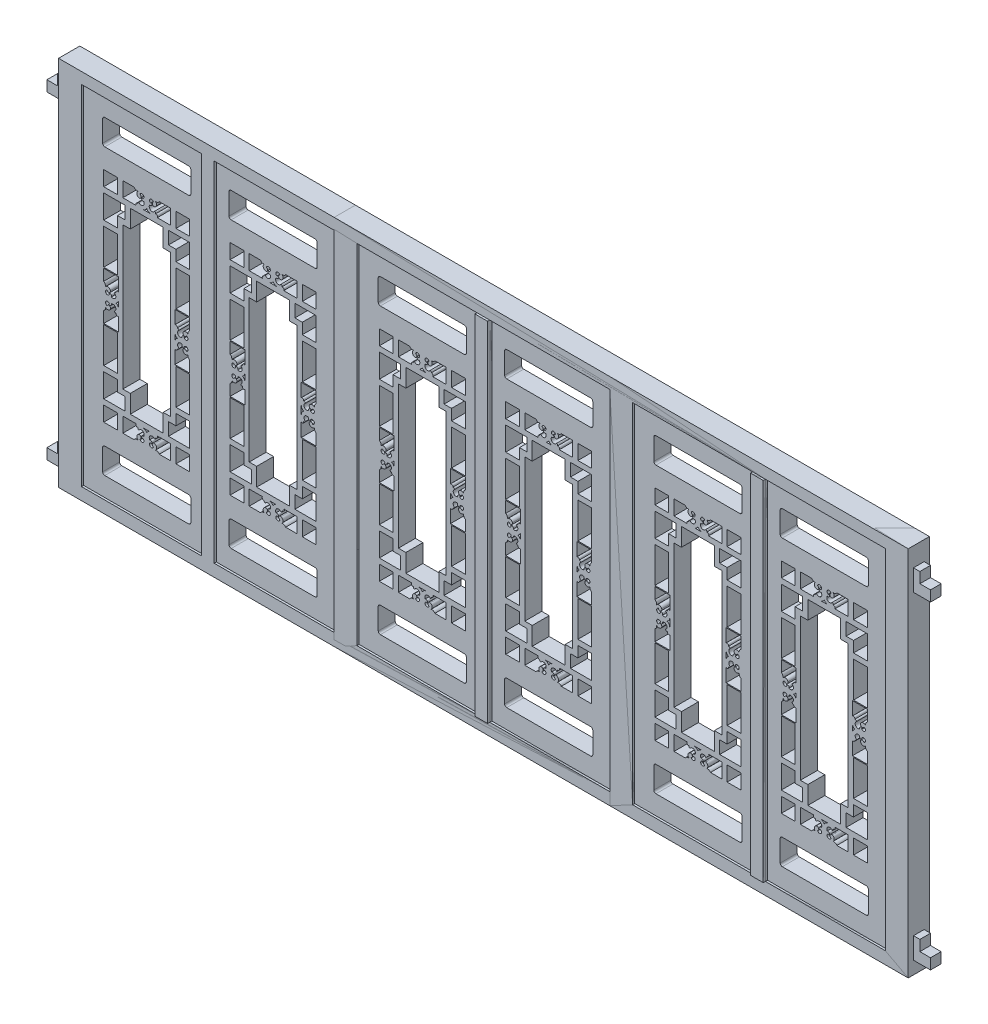
SolidWorks part; units mm, degrees
material "松木"
ref_plane "前视基准面" through (0, 0, 0) normal (0, 0, 1) x (1, 0, 0)
ref_plane "上视基准面" through (0, 0, 0) normal (0, 1, 0) x (1, 0, 0)
ref_plane "右视基准面" through (0, 0, 0) normal (1, 0, 0) x (0, 0, -1)
sketch "Sketch1" plane through (0, 0, 0) normal (0, 0, 1) x (1, 0, 0)
  line L0 (0, 0) -> (0, 1640)
  line L1 (0, 1640) -> (595, 1640)
  line L2 (595, 1640) -> (595, 0)
  line L3 (595, 0) -> (0, 0)
  dimension "D1" = 1640
  dimension "D2" = 595
extrude "Boss-Extrude1" add sketch "Sketch1" along normal blind 180
sketch "Sketch2" plane through (0, 0, 0) normal (0, 0, -1) x (-1, 0, 0)
  line L0 (-525, 1570) -> (-525, 70)
  line L1 (-525, 70) -> (-70, 70)
  line L2 (-70, 70) -> (-70, 1570)
  line L3 (-70, 1570) -> (-525, 1570)
  line L4 (-595, 0) -> (-595, 1640) construction
  line L5 (-595, 1640) -> (0, 1640) construction
  line L6 (-70, 1410) -> (-525, 1410)
  line L7 (-525, 230) -> (-70, 230)
  line L8 (-70, 1360) -> (-525, 1360)
  line L9 (-70, 280) -> (-525, 280)
  line L10 (-500, 1335) -> (-500, 305)
  line L11 (-500, 305) -> (-95, 305)
  line L12 (-95, 305) -> (-95, 1335)
  line L13 (-95, 1335) -> (-500, 1335)
  line L14 (-95, 1265) -> (-500, 1265)
  line L15 (-95, 1240) -> (-500, 1240)
  line L16 (-95, 375) -> (-500, 375)
  line L17 (-95, 400) -> (-500, 400)
  line L18 (-160, 1335) -> (-160, 1265)
  line L19 (-435, 1335) -> (-435, 1265)
  line L20 (-410, 1335) -> (-410, 1265)
  line L21 (-185, 1335) -> (-185, 1265)
  line L22 (-435, 375) -> (-435, 305)
  line L23 (-410, 375) -> (-410, 305)
  line L24 (-160, 375) -> (-160, 305)
  line L25 (-185, 375) -> (-185, 305)
  line L26 (-195, 400) -> (-195, 460)
  line L27 (-195, 460) -> (-160, 460)
  line L28 (-160, 460) -> (-160, 1180)
  line L29 (-160, 1180) -> (-195, 1180)
  line L30 (-195, 1180) -> (-195, 1240)
  line L31 (-400, 1240) -> (-400, 1180)
  line L32 (-400, 1180) -> (-435, 1180)
  line L33 (-435, 1180) -> (-435, 460)
  line L34 (-435, 460) -> (-400, 460)
  line L35 (-400, 460) -> (-400, 400)
  line L36 (-220, 1240) -> (-220, 1155)
  line L37 (-220, 1155) -> (-185, 1155)
  line L38 (-185, 1155) -> (-185, 485)
  line L39 (-185, 485) -> (-220, 485)
  line L40 (-220, 485) -> (-220, 400)
  line L41 (-375, 1240) -> (-375, 1155)
  line L42 (-375, 1155) -> (-410, 1155)
  line L43 (-410, 1155) -> (-410, 485)
  line L44 (-410, 485) -> (-375, 485)
  line L45 (-375, 485) -> (-375, 400)
  line L46 (-435, 1129) -> (-500, 1129)
  line L47 (-435, 1104) -> (-500, 1104)
  line L48 (-160, 1129) -> (-95, 1129)
  line L49 (-160, 1104) -> (-95, 1104)
  line L50 (-435, 511) -> (-500, 511)
  line L51 (-435, 536) -> (-500, 536)
  line L52 (-160, 511) -> (-95, 511)
  line L53 (-160, 536) -> (-95, 536)
  line L54 (-435, 937) -> (-500, 937)
  line L55 (-435, 919.4131) -> (-500, 919.4131)
  line L56 (-435, 703) -> (-500, 703)
  line L57 (-435, 728) -> (-500, 728)
  line L58 (-160, 919.4131) -> (-95, 919.4131)
  line L59 (-160, 937) -> (-95, 937)
  line L60 (-160, 703) -> (-95, 703)
  line L61 (-160, 728) -> (-95, 728)
  line L62 (-495, 210) -> (-100, 210)
  line L63 (-90, 200) -> (-90, 100)
  line L64 (-100, 90) -> (-495, 90)
  line L65 (-505, 100) -> (-505, 200)
  line L67 (-495, 1550) -> (-100, 1550)
  line L68 (-505, 1540) -> (-505, 1440)
  line L69 (-495, 1430) -> (-100, 1430)
  line L70 (-90, 1540) -> (-90, 1440)
  arc A0 (-495, 210) -> (-505, 200) centre (-495, 200) ccw
  arc A1 (-90, 200) -> (-100, 210) centre (-100, 200) ccw
  arc A2 (-505, 100) -> (-495, 90) centre (-495, 100) ccw
  arc A3 (-100, 90) -> (-90, 100) centre (-100, 100) ccw
  arc A4 (-495, 1550) -> (-505, 1540) centre (-495, 1540) ccw
  arc A5 (-90, 1540) -> (-100, 1550) centre (-100, 1540) ccw
  arc A6 (-505, 1440) -> (-495, 1430) centre (-495, 1440) ccw
  arc A7 (-100, 1430) -> (-90, 1440) centre (-100, 1440) ccw
  point P62 (-177.5, 1180)
  point P63 (-220, 442.5)
  point P64 (-177.5, 460)
  point P71 (-392.5, 485)
  dimension "D53" = 20
  dimension "D56" = 20
  dimension "D57" = 20
  dimension "D58" = 20
  dimension "D47" = 30
  dimension "D63" = 20
  dimension "D64" = 20
  dimension "D65" = 20
  dimension "D66" = 20
  dimension "D1" = 70
  dimension "D2" = 70
  dimension "D3" = 1500
  dimension "D4" = 455
  dimension "D5" = 160
  dimension "D6" = 160
  dimension "D7" = 50
  dimension "D8" = 50
  dimension "D9" = 25
  dimension "D10" = 25
  dimension "D11" = 25
  dimension "D12" = 25
  dimension "D13" = 70
  dimension "D14" = 25
  dimension "D15" = 25
  dimension "D16" = 70
  dimension "D17" = 65
  dimension "D18" = 65
  dimension "D19" = 25
  dimension "D20" = 25
  dimension "D21" = 100
  dimension "D22" = 100
  dimension "D23" = 60
  dimension "D24" = 60
  dimension "D25" = 35
  dimension "D26" = 35
  dimension "D27" = 100
  dimension "D28" = 35
  dimension "D29" = 60
  dimension "D30" = 60
  dimension "D31" = 25
  dimension "D32" = 25
  dimension "D33" = 25
  dimension "D34" = 25
  dimension "D35" = 25
  dimension "D36" = 25
  dimension "D37" = 25
  dimension "D38" = 25
  dimension "D39" = 111
  dimension "D40" = 25
  dimension "D41" = 111
  dimension "D42" = 25
  dimension "D43" = 167
  dimension "D44" = 17.5869
  dimension "D45" = 25
  dimension "D46" = 167
  dimension "D48" = 30
  dimension "D49" = 20
  dimension "D50" = 30
  dimension "D51" = 10
  dimension "D52" = 10
  dimension "D54" = 10
  dimension "D55" = 10
  dimension "D59" = 20
  dimension "D60" = 20
  dimension "D61" = 20
  dimension "D62" = 20
  dimension "D67" = 30
  dimension "D68" = 30
  dimension "D69" = 30
  dimension "D70" = 30
  dimension "D71" = 30
  dimension "D72" = 30
  dimension "D73" = 30
  dimension "D74" = 30
sketch "草图1" plane through (0, 0, 0) normal (0, 0, -1) x (-1, 0, 0)
  line L0 (-500, 305) -> (-95, 305) construction
  line L1 (-95, 375) -> (-500, 375) construction
  line L2 (-410, 375) -> (-410, 305) construction
  line L3 (-185, 375) -> (-185, 305) construction
  line L6 (-347.4491, 375) -> (-315.5, 375)
  line L7 (-279.5, 375) -> (-247.5509, 375)
  line L8 (-356.6733, 305) -> (-238.3267, 305)
  line L9 (-347.4491, 375) -> (-410, 375)
  line L10 (-410, 375) -> (-410, 305)
  line L11 (-410, 305) -> (-356.6733, 305)
  line L12 (-315.5, 375) -> (-279.5, 375)
  line L13 (-238.3267, 305) -> (-185, 305)
  line L14 (-185, 305) -> (-185, 375)
  line L15 (-185, 375) -> (-247.5509, 375)
  line L16 (-500, 707.5) -> (-430, 707.5)
  line L18 (-430, 802) -> (-430, 838)
  line L19 (-430, 707.5) -> (-430, 770.0509)
  line L20 (-430, 932.5) -> (-500, 932.5)
  line L22 (-500, 760.8267) -> (-500, 707.5)
  line L24 (-430, 869.9491) -> (-430, 932.5)
  line L25 (-500, 932.5) -> (-500, 879.1733)
  line L26 (-500, 879.1733) -> (-500, 1640) construction
  line L27 (-595, 707.5) -> (0, 707.5) construction
  line L28 (-595, 0) -> (-595, 1640) construction
  line L29 (0, 1640) -> (0, 0) construction
  line L30 (-500, 0) -> (-500, 760.8267) construction
  line L31 (0, 0) -> (-595, 0) construction
  line L32 (-595, 1640) -> (0, 1640) construction
  arc A0 (-297.5, 362.9626) -> (-315.5, 375) centre (-316.8257, 353.5409) ccw
  arc A1 (-279.5, 375) -> (-297.5, 362.9626) centre (-278.1743, 353.5409) ccw
  arc A2 (-311.5772, 341.0539) -> (-334.4772, 355.321) centre (-322.7578, 348.6199) ccw
  arc A4 (-260.5228, 355.321) -> (-283.4228, 341.0539) centre (-272.2422, 348.6199) ccw
  arc A5 (-347.4491, 375) -> (-339.4787, 363.4423) centre (-341.29, 370.7203) ccw
  arc A6 (-255.5213, 363.4423) -> (-247.5509, 375) centre (-253.71, 370.7203) ccw
  arc A7 (-339.4787, 363.4423) -> (-334.4772, 355.321) centre (-333.2172, 361.6977) ccw
  arc A8 (-260.5228, 355.321) -> (-255.5213, 363.4423) centre (-261.7828, 361.6977) ccw
  arc A9 (-297.5, 336.0027) -> (-311.5772, 341.0539) centre (-304.7324, 337.9882) ccw
  arc A10 (-283.4228, 341.0539) -> (-297.5, 336.0027) centre (-290.2676, 337.9882) ccw
  arc A11 (-311.5772, 341.0539) -> (-320.3587, 328.3114) centre (-314.2948, 333.5296) ccw
  arc A12 (-274.6413, 328.3114) -> (-283.4228, 341.0539) centre (-280.7052, 333.5296) ccw
  arc A13 (-315.214, 331.0064) -> (-320.3587, 328.3114) centre (-316.5099, 327.2221) ccw
  arc A14 (-274.6413, 328.3114) -> (-279.786, 331.0064) centre (-278.4901, 327.2221) ccw
  arc A16 (-279.786, 331.0064) -> (-265.6848, 320.9352) centre (-275, 322.8) ccw
  arc A17 (-329.3152, 320.9352) -> (-334.7689, 337.0364) centre (-332, 329) ccw
  arc A18 (-260.2311, 337.0364) -> (-265.6848, 320.9352) centre (-263, 329) ccw
  arc A19 (-329.3152, 320.9352) -> (-315.214, 331.0064) centre (-320, 322.8) ccw
  arc A20 (-463.9461, 834.0772) -> (-476.6886, 842.8587) centre (-471.4704, 836.7948) ccw
  arc A21 (-334.7689, 337.0364) -> (-338.5296, 312.5413) centre (-330.2084, 323.8) ccw
  arc A23 (-338.5296, 312.5413) -> (-356.6733, 305) centre (-343, 297.7) ccw
  arc A24 (-238.3267, 305) -> (-256.4704, 312.5413) centre (-252, 297.7) ccw
  arc A25 (-256.4704, 312.5413) -> (-260.2311, 337.0364) centre (-264.7916, 323.8) ccw
  arc A26 (-473.9936, 837.714) -> (-476.6886, 842.8587) centre (-477.7779, 839.0099) ccw
  arc A27 (-463.9461, 805.9228) -> (-462.5046, 806.773) centre (-467.0118, 812.7676) ccw
  arc A28 (-484.0648, 851.8152) -> (-467.9636, 857.2689) centre (-476, 854.5) ccw
  arc A29 (-430, 869.9491) -> (-441.5577, 861.9787) centre (-434.2797, 863.79) ccw
  arc A30 (-467.9636, 857.2689) -> (-492.4587, 861.0296) centre (-481.2, 852.7084) ccw
  arc A31 (-442.0374, 820) -> (-430, 838) centre (-451.4591, 839.3257) ccw
  arc A32 (-441.5577, 861.9787) -> (-449.679, 856.9772) centre (-443.3023, 855.7172) ccw
  arc A33 (-467.9636, 782.7311) -> (-484.0648, 788.1848) centre (-476, 785.5) ccw
  arc A34 (-476.6886, 797.1413) -> (-463.9461, 805.9228) centre (-471.4704, 803.2052) ccw
  arc A35 (-476.6886, 797.1413) -> (-473.9936, 802.286) centre (-477.7779, 800.9901) ccw
  arc A36 (-441.5577, 778.0213) -> (-430, 770.0509) centre (-434.2797, 776.21) ccw
  arc A37 (-492.4587, 778.9704) -> (-467.9636, 782.7311) centre (-481.2, 787.2916) ccw
  arc A38 (-449.679, 783.0228) -> (-463.9461, 805.9228) centre (-456.3801, 794.7422) ccw
  arc A39 (-484.0648, 851.8152) -> (-473.9936, 837.714) centre (-482.2, 842.5) ccw
  arc A40 (-500, 760.8267) -> (-492.4587, 778.9704) centre (-507.3, 774.5) ccw
  arc A41 (-449.679, 783.0228) -> (-441.5577, 778.0213) centre (-443.3023, 784.2828) ccw
  arc A42 (-473.9936, 802.286) -> (-484.0648, 788.1848) centre (-482.2, 797.5) ccw
  arc A43 (-463.9461, 834.0772) -> (-449.679, 856.9772) centre (-456.3801, 845.2578) ccw
  arc A44 (-492.4587, 861.0296) -> (-500, 879.1733) centre (-507.3, 865.5) ccw
  arc A46 (-430, 802) -> (-442.0374, 820) centre (-451.4591, 800.6743) ccw
  arc A48 (-462.5046, 833.227) -> (-463.9461, 834.0772) centre (-467.0118, 827.2324) ccw
  dimension "D5" = 37.0118
  dimension "D6" = 105.2676
  dimension "D11" = 27
  dimension "D12" = 27
  dimension "D13" = 15
  dimension "D10" = 15
  dimension "D15" = 13
  dimension "D16" = 13
  dimension "D2" = 15
  dimension "D3" = 15
  dimension "D8" = 16
  dimension "D9" = 16
  dimension "D18" = 8
  dimension "D19" = 8
  dimension "D24" = 9.5
  dimension "D25" = 19
  dimension "D30" = 17
  dimension "D31" = 17
  dimension "D36" = 28
  dimension "D37" = 95
  dimension "D40" = 31
  dimension "D41" = 31
  dimension "D4" = 37.0118
  dimension "D7" = 105.2676
  dimension "D14" = 95.7052
  dimension "D17" = 95.7052
  dimension "D20" = 47.7779
  dimension "D21" = 47.7779
  dimension "D22" = 93.4901
  dimension "D23" = 93.4901
  dimension "D26" = 90
  dimension "D27" = 90
  dimension "D28" = 52.2
  dimension "D29" = 52.2
  dimension "D32" = 24
  dimension "D33" = 24
  dimension "D34" = 78
  dimension "D35" = 78
  dimension "D38" = 18.8
  dimension "D39" = 707.5
  dimension "D42" = 7.3
  dimension "D43" = 7.3
  dimension "D44" = 67
  dimension "D45" = 67
sketch "草图5" plane through (0, 0, 0) normal (0, 0, -1) x (-1, 0, 0)
sketch "草图6" plane through (0, 0, 180) normal (0, 0, 1) x (1, 0, 0)
  line L0 (0, 1640) -> (0, 0)
  line L1 (0, 0) -> (595, 0)
  line L2 (595, 0) -> (595, 1640)
  line L3 (595, 1640) -> (0, 1640)
extrude "切除-拉伸2" cut sketch "草图6" against normal blind 100
extrude "切除-拉伸3" cut sketch "草图1" against normal blind 100 contours A23 A21 A17 A19 A13 A11 A9 A2 A7 A5 L9 L10 L11 | A25 A24 L13 L14 L15 A6 A8 A4 A10 A12 A14 A16 A18 | A1 L12 A0 region at (368.1315, 340.5137, 0) region at (297.5, 371.6597, 0) region at (226.8685, 340.5137, 0)
extrude "切除-拉伸5" cut sketch "Sketch2" against normal through all contours L64 A3 L63 A1 L62 A0 L65 A2 | L22 L16 L10 L11 | L16 L24 L11 L12 | L33 L50 L10 L17 L35 L34 | L52 L28 L27 L26 L17 L12 | L33 L56 L10 L51 | L60 L28 L53 L12 | L44 L45 L17 L40 L39 L38 L37 L36 L15 L41 L42 L43 | L54 L33 L47 L10 | L28 L59 L12 L49 | L28 L48 L12 L15 L30 L29 | L13 L18 L14 L12 | L19 L13 L10 L14 | L46 L33 L32 L31 L15 L10 | L69 A7 L70 A5 L67 A4 L68 A6 region at (467.5, 1300, 0) region at (456.2279, 1190.2488, 0) region at (467.5, 1020.5, 0) region at (297.5, 820, 0) region at (127.5, 1300, 0) region at (138.7721, 1190.2488, 0) region at (467.5, 619.5, 0) region at (127.5, 1020.5, 0) region at (456.2279, 449.7512, 0) region at (138.7721, 449.7512, 0) region at (467.5, 340, 0) region at (127.5, 619.5, 0) region at (127.5, 340, 0) region at (297.5, 150, 0) region at (297.5, 1490, 0)
ref_plane "基准面1" through (0, 820, 0) normal (0, 1, 0) x (1, 0, 0)
mirror "镜向1" about plane through (0, 820, 0) normal (0, 1, 0) of "切除-拉伸3"
extrude "切除-拉伸8" cut sketch "草图1<5>" against normal through all contours A48 A43 A32 A29 L24 L20 L25 A44 A30 A28 A39 A26 A20 | A35 A42 A33 A37 A40 L22 L16 L19 A36 A41 A38 A27 A34 | A31 L18 A46 region at (464.4863, 749.3685, 0) region at (464.4863, 890.6315, 0)
sketch "草图1<5>" plane through (0, 0, 0) normal (0, 0, -1) x (-1, 0, 0) same geometry as "草图1"
ref_plane "基准面3" through (297.5, 0, 0) normal (-1, 0, 0) x (0, 0, 1)
mirror "镜向3" about plane through (297.5, 0, 0) normal (-1, 0, 0) of "切除-拉伸8"
ref_plane "基准面4" through (605, 0, 0) normal (1, 0, 0) x (0, 0, -1)
pattern_linear "阵列(线性)1" count 2 spacing 595 along (1, 0, 0) of bodies 117 119
sketch "草图7" plane through (0, 0, 0) normal (0, 0, 1) x (1, 0, 0)
  line L0 (1297.5, 1640) -> (2487.5, 1640)
  line L1 (1190, 1640) -> (0, 1640)
  line L2 (1190, 1640) -> (1190, 0)
  line L3 (1190, 0) -> (0, 0)
  line L4 (0, 1640) -> (0, 0)
  line L5 (2487.5, 1640) -> (2487.5, 0)
  line L6 (2487.5, 0) -> (1297.5, 0)
  line L7 (1297.5, 0) -> (1297.5, 1640)
  line L8 (2595, 1640) -> (3785, 1640)
  line L9 (3785, 1640) -> (3785, 0)
  line L10 (3785, 0) -> (2595, 0)
  line L11 (2595, 0) -> (2595, 1640)
  line L12 (3892.5, 1692.5) -> (3892.5, -57.5)
  line L13 (3892.5, -57.5) -> (-107.5, -57.5)
  line L14 (-107.5, -57.5) -> (-107.5, 1692.5)
  line L15 (-107.5, 1692.5) -> (3892.5, 1692.5)
  dimension "D1" = 4000
  dimension "D2" = 1190
  dimension "D3" = 1190
  dimension "D4" = 107.5
  dimension "D5" = 107.5
  dimension "D6" = 107.5
  dimension "D7" = 1750
  dimension "D8" = 52.5
extrude "凸台-拉伸2" add sketch "草图7" along normal blind 90 and the other way blind 10 contours L15 L12 L13 L14 | L11 L8 L9 L10 | L7 L0 L5 L6 | L2 L1 L4 L3
sketch "草图8" plane through (0, 0, 0) normal (0, 0, -1) x (-1, 0, 0)
  line L0 (-595, 1640) -> (-565, 1640)
  line L1 (-1190, 1640) -> (0, 1640) construction
  line L2 (-565, 1640) -> (-565, 0)
  line L3 (0, 0) -> (-1190, 0) construction
  line L4 (-565, 0) -> (-625, 0)
  line L5 (-625, 0) -> (-625, 1640)
  line L6 (-1190, 1640) -> (0, 1640) construction
  line L7 (-625, 1640) -> (-595, 1640)
  dimension "D1" = 30
  dimension "D2" = 30
extrude "凸台-拉伸3" add sketch "草图8" along normal blind 10 and the other way blind 90
sketch "草图9" plane through (0, 0, 0) normal (0, 0, 1) x (1, 0, 0)
  line L0 (1297.5, 1640) -> (2487.5, 1640) construction
  line L1 (2487.5, 0) -> (1297.5, 0) construction
  line L2 (1922.5, 1640) -> (1862.5, 1640)
  line L3 (1922.5, 1640) -> (1922.5, 0)
  line L4 (1922.5, 0) -> (1862.5, 0)
  line L5 (1862.5, 1640) -> (1862.5, 0)
  line L6 (2595, 1640) -> (3785, 1640) construction
  line L7 (3220, 1640) -> (3160, 1640)
  line L8 (3220, 1640) -> (3220, 0)
  line L9 (3220, 0) -> (3160, 0)
  line L10 (3160, 1640) -> (3160, 0)
  dimension "D1" = 565
  dimension "D2" = 60
  dimension "D3" = 565
  dimension "D4" = 60
extrude "凸台-拉伸4" add sketch "草图9" along normal blind 100 contours L8 L7 L10 L9 | L3 L2 L5 L4
pattern_linear "阵列(线性)2" count 3 spacing 1297.5 along (1, 0, 0) of bodies 127
sketch "草图11" plane through (0, 0, 100) normal (0, 0, 1) x (1, 0, 0)
  line L1 (3892.5, 1692.5) -> (6487.5, 1692.5)
  line L2 (3892.5, 1692.5) -> (3892.5, -57.5)
  line L3 (3892.5, -57.5) -> (6487.5, -57.5)
  line L4 (6487.5, 1692.5) -> (6487.5, -57.5)
extrude "切除-拉伸9" cut sketch "草图11" against normal through all
ref_plane "基准面6" through (-107.5, -57.5, 90) normal (-1, 0, 0) x (0, 0, 1)
sketch "草图12" plane through (-107.5, 0, 0) normal (-1, 0, 0) x (0, 0, 1)
  line L0 (-10, -57.5) -> (90, -57.5) construction
  line L1 (15, 102.5) -> (65, 102.5)
  line L2 (15, 102.5) -> (15, 2.5)
  line L3 (15, 2.5) -> (65, 2.5)
  line L4 (65, 102.5) -> (65, 2.5)
  line L5 (15, 52.5) -> (65, 52.5)
  point P6 (40, 102.5)
  point P7 (40, -57.5)
  dimension "D1" = 60
  dimension "D2" = 50
  dimension "D3" = 100
  dimension "D4" = 50
extrude "凸台-拉伸5" add sketch "草图12" along normal blind 80 contours L5 L2 L3 L4 | L2 L1 L4 L3 region at (-107.5, 27.5, 40)
sketch "草图13" plane through (-187.5, 0, 0) normal (-1, 0, 0) x (0, 0, 1)
  line L0 (15, 102.5) -> (15, 2.5) construction
  line L1 (15, 52.5) -> (65, 52.5)
  line L2 (15, 52.5) -> (15, 2.5)
  line L3 (15, 2.5) -> (65, 2.5)
  line L4 (65, 52.5) -> (65, 2.5)
  line L5 (65, 102.5) -> (65, 2.5) construction
  line L6 (15, 52.5) -> (15, 102.5)
  line L7 (15, 102.5) -> (65, 102.5)
  line L8 (65, 102.5) -> (65, 52.5)
  line M1 (65, 2.5) -> (65, 102.5)
  line M2 (65, 102.5) -> (15, 102.5)
  line M3 (15, 102.5) -> (15, 2.5)
  dimension "D1" = 50
extrude "切除-拉伸10" cut sketch "草图13" against normal blind 50 contours L1 M3 M1 M2 region at (-187.5, 77.5, 40)
pattern_linear "阵列(线性)3" count 2 spacing 1500 along (0, 1, 0) of "切除-拉伸10", "凸台-拉伸5"
ref_plane "基准面7" through (1892.5, -57.5, 90) normal (-1, 0, 0) x (0, 0, 1)
mirror "镜向4" about plane through (1892.5, -57.5, 90) normal (-1, 0, 0) of "凸台-拉伸5", "切除-拉伸10", "阵列(线性)3"
